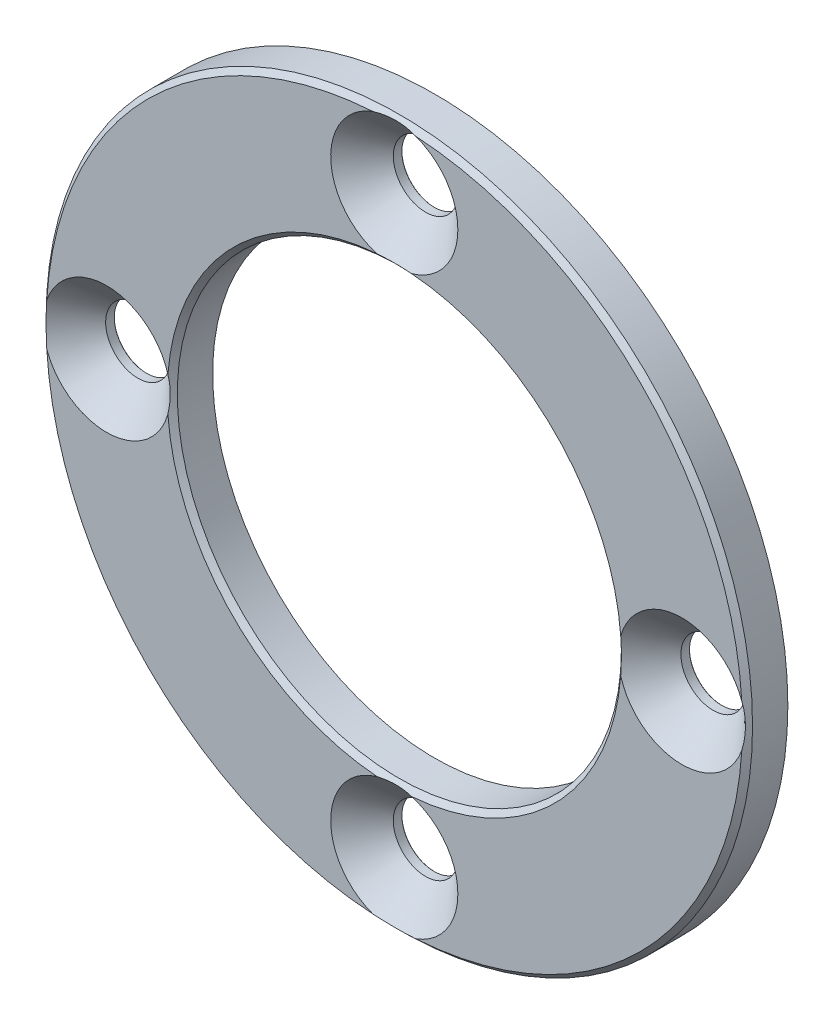
SolidWorks part; units mm, degrees
material "2018 合金"
ref_plane "正面" through (0, 0, 0) normal (0, 0, 1) x (1, 0, 0)
ref_plane "平面" through (0, 0, 0) normal (0, 1, 0) x (1, 0, 0)
ref_plane "右側面" through (0, 0, 0) normal (1, 0, 0) x (0, 0, -1)
sketch "ｽｹｯﾁ1" plane through (0, 0, 0) normal (0, 0, 1) x (1, 0, 0)
  circle A0 centre (0, 0) radius 17.5
  circle A2 centre (0, 0) radius 11
  point P3 (0, 0)
  point P4 (0, 0)
  point P6 (0, 0)
  point P7 (0, 0)
  dimension "D1" = 35
  dimension "D2" = 22
extrude "ﾎﾞｽ - 押し出し1" add sketch "ｽｹｯﾁ1" along normal blind 2
hole_wizard "M3 丸皿ねじ用皿穴1" positions "ｽｹｯﾁ3" profile "ｽｹｯﾁ4" countersink size "M3" standard "JIS" end condition through all
sketch "ｽｹｯﾁ3" plane through (0, 0, 2) normal (0, 0, 1) x (1, 0, 0)
  point P0 (0, 14.25)
  point P9 (14.25, 0)
  point P10 (0, -14.25)
  point P11 (-14.25, 0)
  point P12 (0, 0)
  dimension "D1" = 14.25
  dimension "D2" = 4
sketch "ｽｹｯﾁ4" plane through (0, 14.25, 2) normal (1, 0, 0) x (0, -1, 0)
  line L0 (0, 0) -> (0, 2)
  line L1 (0, 2) -> (1.625, 2)
  line L2 (1.6, 1.975) -> (1.6, 1.55)
  line L3 (1.6, 1.55) -> (3.15, 0)
  line L5 (3.15, 0) -> (0, 0)
  line L6 (-1.6, 1.55) -> (-3.15, 0) construction
  line L7 (1.625, 2) -> (1.6, 1.975)
  line L8 (-1.625, 2) -> (-1.6, 1.975) construction
  line L11 (0, -6.35) -> (0, 107.95) construction
  dimension "通し穴の直径" = 3.2
  dimension "通し穴の深さ" = 2
  dimension "表面の皿穴の直径" = 6.3
  dimension "表面の皿穴の角度" = 90
  dimension "裏面の皿穴の直径" = 3.25
  dimension "裏面の皿穴の角度" = 90
chamfer "面取り1" distance 0.25 angle 45 2 edges at (17.5, 0, 2) (11, 0, 2)
